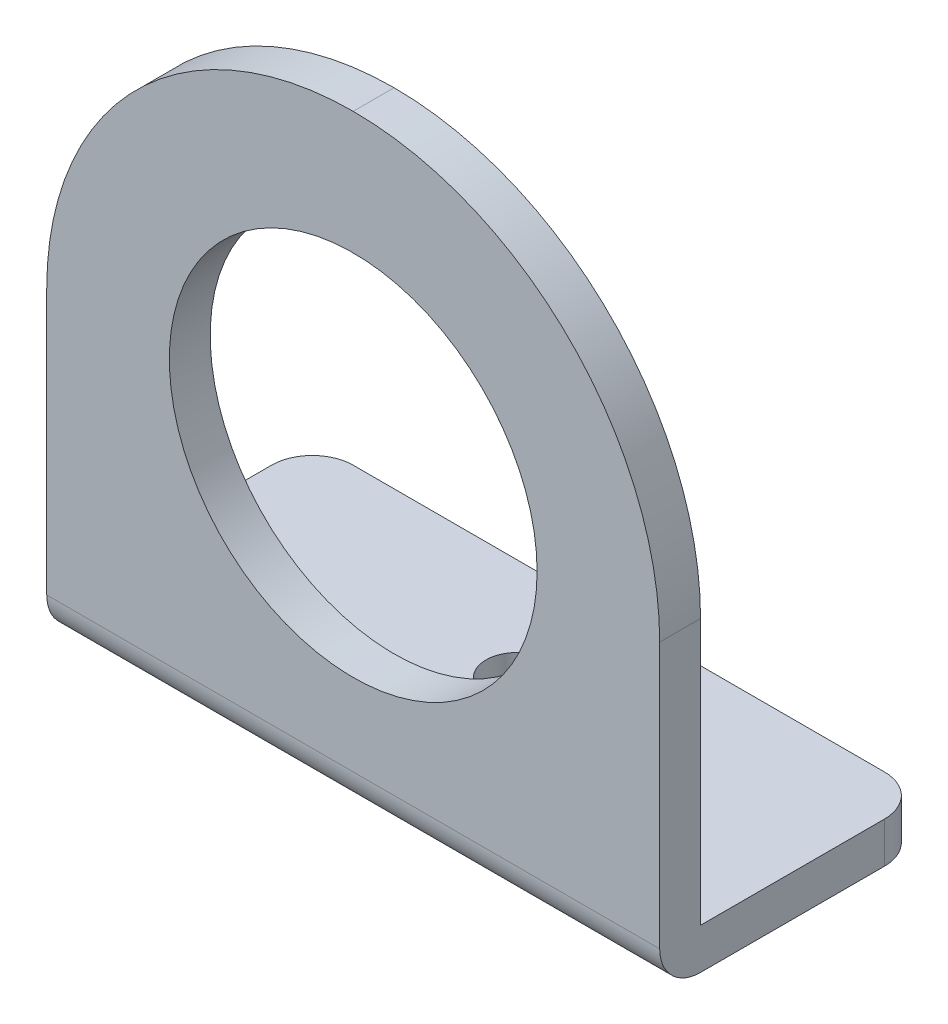
SolidWorks part; units mm, degrees
ref_plane "Front Plane" through (0, 0, 0) normal (0, 0, 1) x (1, 0, 0)
ref_plane "Top Plane" through (0, 0, 0) normal (0, 1, 0) x (1, 0, 0)
ref_plane "Right Plane" through (0, 0, 0) normal (1, 0, 0) x (0, 0, -1)
sketch "Sketch1" plane through (0, 0, 0) normal (0, 0, 1) x (1, 0, 0)
  line L1 (15, 15) -> (-15, 15)
  line L2 (15, 15) -> (15, -15)
  line L3 (15, -15) -> (-15, -15)
  line L4 (-15, 15) -> (-15, -15)
  line L5 (15, 15) -> (-15, -15) construction
  line L6 (15, -15) -> (-15, 15) construction
  point P0 (0, 0)
  dimension "D1" = 30
  dimension "D2" = 30
extrude "Boss-Extrude1" add sketch "Sketch1" along normal blind 2
sketch "Sketch2" plane through (0, 0, 2) normal (0, 0, 1) x (1, 0, 0)
  circle A0 centre (0, 0) radius 9
  point P2 (0, 0)
  dimension "D1" = 18
extrude "Cut-Extrude1" cut sketch "Sketch2" against normal through all contours A0
fillet "Fillet1" radius 15 2 edges at (-15, 15, 1) (15, 15, 1)
sketch "Sketch3" plane through (0, 0, 0) normal (0, 0, -1) x (-1, 0, 0)
  line L0 (15, 0) -> (15, -15) construction
  line L1 (-15, -15) -> (15, -15)
  line L2 (-15, -15) -> (-15, -13)
  line L3 (-15, -13) -> (15, -13)
  line L4 (15, -15) -> (15, -13)
  dimension "D1" = 2
extrude "Boss-Extrude2" add sketch "Sketch3" along normal blind 11
sketch "Sketch4" plane through (0, -13, 0) normal (0, 1, 0) x (1, 0, 0)
  line L0 (-15, 11) -> (15, 11) construction
  circle A0 centre (0, 6) radius 1.5
  point P2 (0, 0)
  dimension "D1" = 3
  dimension "D2" = 5
extrude "Cut-Extrude2" cut sketch "Sketch4" against normal through all
fillet "Fillet2" radius 2 3 edges at (0, -15, 2) (-15, -14, -11) (15, -14, -11)
